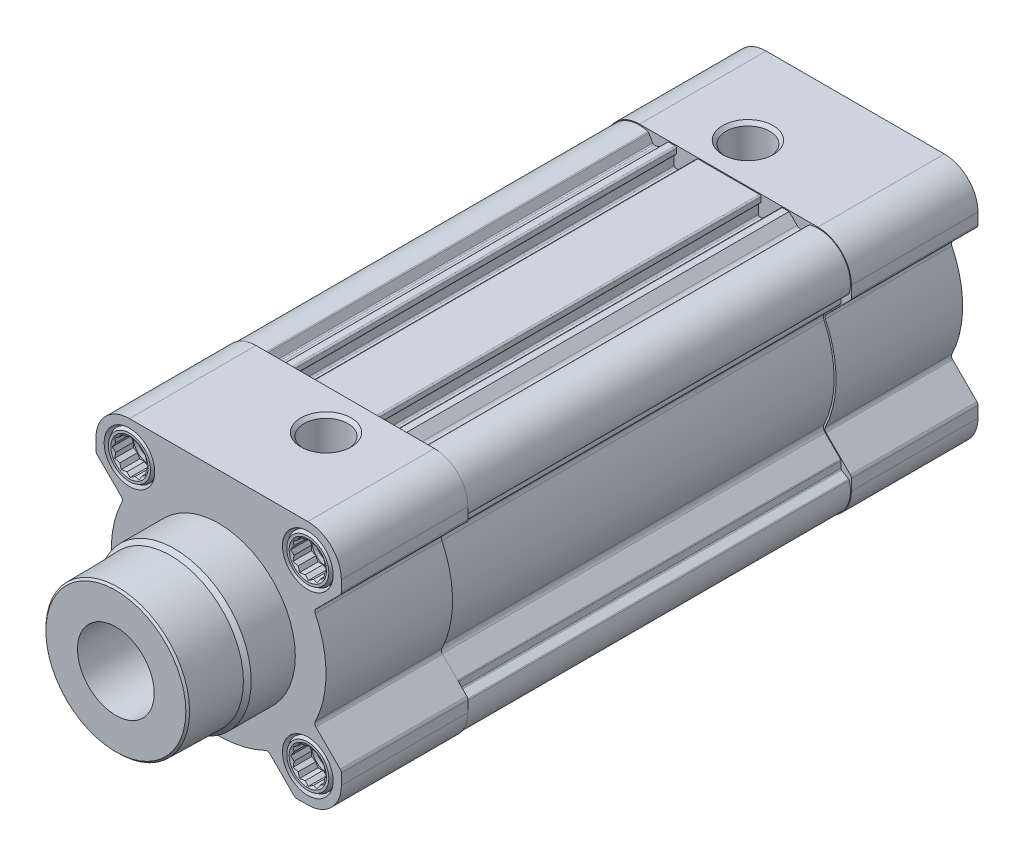
SolidWorks part; units mm, degrees
ref_plane "Front Plane" through (0, 0, 0) normal (0, 0, 1) x (1, 0, 0)
ref_plane "Top Plane" through (0, 0, 0) normal (0, 1, 0) x (1, 0, 0)
ref_plane "Right Plane" through (0, 0, 0) normal (1, 0, 0) x (0, 0, -1)
ref_plane "Plane1" through (0, 0, -33) normal (0, 0, 1) x (1, 0, 0)
sketch "Sketch1" plane through (0, 0, -33) normal (0, 0, 1) x (1, 0, 0)
  line L0 (-31.7071, 19.6863) -> (-25.385, 13.3642)
  line L1 (-25.385, -13.3642) -> (-31.7071, -19.6863)
  line L2 (-32, -20.3934) -> (-32, -23.25)
  line L3 (-23.25, -32) -> (-20.3934, -32)
  line L4 (-19.6863, -31.7071) -> (-13.3642, -25.385)
  line L5 (13.3642, -25.385) -> (19.6863, -31.7071)
  line L6 (20.3934, -32) -> (23.25, -32)
  line L7 (32, -23.25) -> (32, -20.3934)
  line L8 (31.7071, -19.6863) -> (25.385, -13.3642)
  line L9 (25.385, 13.3642) -> (31.7071, 19.6863)
  line L10 (32, 20.3934) -> (32, 23.25)
  line L11 (23.25, 32) -> (-23.25, 32)
  line L12 (-32, 23.25) -> (-32, 20.3934)
  arc A0 (-32, 20.3934) -> (-31.7071, 19.6863) centre (-31, 20.3934) ccw
  arc A1 (-25.385, 13.3642) -> (-25.1924, 12.2206) centre (-26.0921, 12.6571) cw
  arc A2 (-25.1924, 12.2206) -> (-25.1924, -12.2206) centre (0, 0) ccw
  arc A3 (-25.1924, -12.2206) -> (-25.385, -13.3642) centre (-26.0921, -12.6571) cw
  arc A4 (-31.7071, -19.6863) -> (-32, -20.3934) centre (-31, -20.3934) ccw
  arc A5 (-32, -23.25) -> (-23.25, -32) centre (-23.25, -23.25) ccw
  arc A6 (-20.3934, -32) -> (-19.6863, -31.7071) centre (-20.3934, -31) ccw
  arc A7 (-13.3642, -25.385) -> (-12.2206, -25.1924) centre (-12.6571, -26.0921) cw
  arc A8 (-12.2206, -25.1924) -> (12.2206, -25.1924) centre (0, 0) ccw
  arc A9 (12.2206, -25.1924) -> (13.3642, -25.385) centre (12.6571, -26.0921) cw
  arc A10 (19.6863, -31.7071) -> (20.3934, -32) centre (20.3934, -31) ccw
  arc A11 (23.25, -32) -> (32, -23.25) centre (23.25, -23.25) ccw
  arc A12 (32, -20.3934) -> (31.7071, -19.6863) centre (31, -20.3934) ccw
  arc A13 (25.385, -13.3642) -> (25.1924, -12.2206) centre (26.0921, -12.6571) cw
  arc A14 (25.1924, -12.2206) -> (25.1924, 12.2206) centre (0, 0) ccw
  arc A15 (25.1924, 12.2206) -> (25.385, 13.3642) centre (26.0921, 12.6571) cw
  arc A16 (31.7071, 19.6863) -> (32, 20.3934) centre (31, 20.3934) ccw
  arc A17 (32, 23.25) -> (23.25, 32) centre (23.25, 23.25) ccw
  arc A18 (-23.25, 32) -> (-32, 23.25) centre (-23.25, 23.25) ccw
extrude "Boss-Extrude1" add sketch "Sketch1" along normal blind 33
sketch "Sketch2" plane through (0, 0, -33) normal (0, 0, 1) x (1, 0, 0)
  line L0 (-31.75, 20.0827) -> (-25.2961, 13.6289)
  line L1 (-25.2961, -13.6289) -> (-31.75, -20.0827)
  line L2 (-31.75, -20.0827) -> (-31.75, -23.5)
  line L3 (-23.5, -31.75) -> (-20.0827, -31.75)
  line L4 (-20.0827, -31.75) -> (-13.6289, -25.2961)
  line L5 (13.6289, -25.2961) -> (20.0827, -31.75)
  line L6 (20.0827, -31.75) -> (23.5, -31.75)
  line L7 (31.75, -23.5) -> (31.75, -20.0827)
  line L8 (31.75, -20.0827) -> (25.2961, -13.6289)
  line L9 (25.2961, 13.6289) -> (31.75, 20.0827)
  line L10 (31.75, 20.0827) -> (31.75, 23.5)
  line L11 (23.5, 31.75) -> (-23.5, 31.75)
  line L12 (-31.75, 23.5) -> (-31.75, 20.0827)
  arc A0 (-25.2961, 13.6289) -> (-25.0028, 11.9226) centre (-26.3568, 12.5682) cw
  arc A1 (-25.0028, 11.9226) -> (-25.0028, -11.9226) centre (0, 0) ccw
  arc A2 (-25.0028, -11.9226) -> (-25.2961, -13.6289) centre (-26.3568, -12.5682) cw
  arc A3 (-31.75, -23.5) -> (-23.5, -31.75) centre (-23.5, -23.5) ccw
  arc A4 (-13.6289, -25.2961) -> (-11.9226, -25.0028) centre (-12.5682, -26.3568) cw
  arc A5 (-11.9226, -25.0028) -> (11.9226, -25.0028) centre (0, 0) ccw
  arc A6 (11.9226, -25.0028) -> (13.6289, -25.2961) centre (12.5682, -26.3568) cw
  arc A7 (23.5, -31.75) -> (31.75, -23.5) centre (23.5, -23.5) ccw
  arc A8 (25.2961, -13.6289) -> (25.0028, -11.9226) centre (26.3568, -12.5682) cw
  arc A9 (25.0028, -11.9226) -> (25.0028, 11.9226) centre (0, 0) ccw
  arc A10 (25.0028, 11.9226) -> (25.2961, 13.6289) centre (26.3568, 12.5682) cw
  arc A11 (31.75, 23.5) -> (23.5, 31.75) centre (23.5, 23.5) ccw
  arc A12 (-23.5, 31.75) -> (-31.75, 23.5) centre (-23.5, 23.5) ccw
extrude "Boss-Extrude2" add sketch "Sketch2" against normal blind 100
sketch "Sketch3" plane through (0, 0, -33) normal (0, 0, 1) x (1, 0, 0)
  line L0 (-38.4, -38.4) -> (38.4, -38.4)
  line L1 (38.4, -38.4) -> (38.4, 38.4)
  line L2 (38.4, 38.4) -> (-38.4, 38.4)
  line L3 (-38.4, 38.4) -> (-38.4, -38.4)
  line L4 (-20.8477, -31.2378) -> (-19.8155, -29.45)
  line L5 (-19.4691, -29.25) -> (-17.7484, -29.25)
  line L6 (-17.4656, -29.1328) -> (-13.4788, -25.146)
  line L7 (13.4788, -25.146) -> (17.4656, -29.1328)
  line L8 (17.7484, -29.25) -> (19.4691, -29.25)
  line L9 (19.8155, -29.45) -> (20.8477, -31.2378)
  line L10 (31.2378, -20.8477) -> (29.45, -19.8155)
  line L11 (29.25, -19.4691) -> (29.25, -17.7484)
  line L12 (29.1328, -17.4656) -> (25.146, -13.4788)
  line L13 (25.146, 13.4788) -> (29.1328, 17.4656)
  line L14 (29.25, 17.7484) -> (29.25, 19.4691)
  line L15 (29.45, 19.8155) -> (31.2378, 20.8477)
  line L16 (20.8477, 31.2378) -> (19.8155, 29.45)
  line L17 (19.4691, 29.25) -> (18.8713, 29.25)
  line L18 (17.8107, 29.6893) -> (15.75, 31.75)
  line L19 (15.75, 31.75) -> (14, 31.75)
  line L20 (13.6, 31.35) -> (13.6, 30.15)
  line L21 (13.8, 29.95) -> (14.05, 29.95)
  line L22 (14.25, 29.75) -> (14.25, 27.15)
  line L23 (13.85, 26.75) -> (8.15, 26.75)
  line L24 (7.75, 27.15) -> (7.75, 29.75)
  line L25 (7.95, 29.95) -> (8.2, 29.95)
  line L26 (8.4, 30.15) -> (8.4, 31.35)
  line L27 (8, 31.75) -> (-8, 31.75)
  line L28 (-8.4, 31.35) -> (-8.4, 30.15)
  line L29 (-8.2, 29.95) -> (-7.95, 29.95)
  line L30 (-7.75, 29.75) -> (-7.75, 27.15)
  line L31 (-8.15, 26.75) -> (-13.85, 26.75)
  line L32 (-14.25, 27.15) -> (-14.25, 29.75)
  line L33 (-14.05, 29.95) -> (-13.8, 29.95)
  line L34 (-13.6, 30.15) -> (-13.6, 31.35)
  line L35 (-14, 31.75) -> (-15.75, 31.75)
  line L36 (-15.75, 31.75) -> (-17.8107, 29.6893)
  line L37 (-18.8713, 29.25) -> (-19.4691, 29.25)
  line L38 (-19.8155, 29.45) -> (-20.8477, 31.2378)
  line L39 (-31.2378, 20.8477) -> (-29.45, 19.8155)
  line L40 (-29.25, 19.4691) -> (-29.25, 17.7484)
  line L41 (-29.1328, 17.4656) -> (-25.146, 13.4788)
  line L42 (-25.146, -13.4788) -> (-29.1328, -17.4656)
  line L43 (-29.25, -17.7484) -> (-29.25, -19.4691)
  line L44 (-29.45, -19.8155) -> (-31.2378, -20.8477)
  arc A0 (-31.4221, -21.0831) -> (-21.0831, -31.4221) centre (-23.4, -23.4) ccw
  arc A1 (-21.0831, -31.4221) -> (-20.8477, -31.2378) centre (-21.1941, -31.0378) ccw
  arc A2 (-19.8155, -29.45) -> (-19.4691, -29.25) centre (-19.4691, -29.65) cw
  arc A3 (-17.7484, -29.25) -> (-17.4656, -29.1328) centre (-17.7484, -28.85) ccw
  arc A4 (-13.4788, -25.146) -> (-11.7758, -24.8512) centre (-12.4181, -26.2067) cw
  arc A5 (-11.7758, -24.8512) -> (11.7758, -24.8512) centre (0, 0) ccw
  arc A6 (11.7758, -24.8512) -> (13.4788, -25.146) centre (12.4181, -26.2067) cw
  arc A7 (17.4656, -29.1328) -> (17.7484, -29.25) centre (17.7484, -28.85) ccw
  arc A8 (19.4691, -29.25) -> (19.8155, -29.45) centre (19.4691, -29.65) cw
  arc A9 (20.8477, -31.2378) -> (21.0831, -31.4221) centre (21.1941, -31.0378) ccw
  arc A10 (21.0831, -31.4221) -> (31.4221, -21.0831) centre (23.4, -23.4) ccw
  arc A11 (31.4221, -21.0831) -> (31.2378, -20.8477) centre (31.0378, -21.1941) ccw
  arc A12 (29.45, -19.8155) -> (29.25, -19.4691) centre (29.65, -19.4691) cw
  arc A13 (29.25, -17.7484) -> (29.1328, -17.4656) centre (28.85, -17.7484) ccw
  arc A14 (25.146, -13.4788) -> (24.8512, -11.7758) centre (26.2067, -12.4181) cw
  arc A15 (24.8512, -11.7758) -> (24.8512, 11.7758) centre (0, 0) ccw
  arc A16 (24.8512, 11.7758) -> (25.146, 13.4788) centre (26.2067, 12.4181) cw
  arc A17 (29.1328, 17.4656) -> (29.25, 17.7484) centre (28.85, 17.7484) ccw
  arc A18 (29.25, 19.4691) -> (29.45, 19.8155) centre (29.65, 19.4691) cw
  arc A19 (31.2378, 20.8477) -> (31.4221, 21.0831) centre (31.0378, 21.1941) ccw
  arc A20 (31.4221, 21.0831) -> (21.0831, 31.4221) centre (23.4, 23.4) ccw
  arc A21 (21.0831, 31.4221) -> (20.8477, 31.2378) centre (21.1941, 31.0378) ccw
  arc A22 (19.8155, 29.45) -> (19.4691, 29.25) centre (19.4691, 29.65) cw
  arc A23 (18.8713, 29.25) -> (17.8107, 29.6893) centre (18.8713, 30.75) cw
  arc A24 (14, 31.75) -> (13.6, 31.35) centre (14, 31.35) ccw
  arc A25 (13.6, 30.15) -> (13.8, 29.95) centre (13.8, 30.15) ccw
  arc A26 (14.05, 29.95) -> (14.25, 29.75) centre (14.05, 29.75) cw
  arc A27 (14.25, 27.15) -> (13.85, 26.75) centre (13.85, 27.15) cw
  arc A28 (8.15, 26.75) -> (7.75, 27.15) centre (8.15, 27.15) cw
  arc A29 (7.75, 29.75) -> (7.95, 29.95) centre (7.95, 29.75) cw
  arc A30 (8.2, 29.95) -> (8.4, 30.15) centre (8.2, 30.15) ccw
  arc A31 (8.4, 31.35) -> (8, 31.75) centre (8, 31.35) ccw
  arc A32 (-8, 31.75) -> (-8.4, 31.35) centre (-8, 31.35) ccw
  arc A33 (-8.4, 30.15) -> (-8.2, 29.95) centre (-8.2, 30.15) ccw
  arc A34 (-7.95, 29.95) -> (-7.75, 29.75) centre (-7.95, 29.75) cw
  arc A35 (-7.75, 27.15) -> (-8.15, 26.75) centre (-8.15, 27.15) cw
  arc A36 (-13.85, 26.75) -> (-14.25, 27.15) centre (-13.85, 27.15) cw
  arc A37 (-14.25, 29.75) -> (-14.05, 29.95) centre (-14.05, 29.75) cw
  arc A38 (-13.8, 29.95) -> (-13.6, 30.15) centre (-13.8, 30.15) ccw
  arc A39 (-13.6, 31.35) -> (-14, 31.75) centre (-14, 31.35) ccw
  arc A40 (-17.8107, 29.6893) -> (-18.8713, 29.25) centre (-18.8713, 30.75) cw
  arc A41 (-19.4691, 29.25) -> (-19.8155, 29.45) centre (-19.4691, 29.65) cw
  arc A42 (-20.8477, 31.2378) -> (-21.0831, 31.4221) centre (-21.1941, 31.0378) ccw
  arc A43 (-21.0831, 31.4221) -> (-31.4221, 21.0831) centre (-23.4, 23.4) ccw
  arc A44 (-31.4221, 21.0831) -> (-31.2378, 20.8477) centre (-31.0378, 21.1941) ccw
  arc A45 (-29.45, 19.8155) -> (-29.25, 19.4691) centre (-29.65, 19.4691) cw
  arc A46 (-29.25, 17.7484) -> (-29.1328, 17.4656) centre (-28.85, 17.7484) ccw
  arc A47 (-25.146, 13.4788) -> (-24.8512, 11.7758) centre (-26.2067, 12.4181) cw
  arc A48 (-24.8512, 11.7758) -> (-24.8512, -11.7758) centre (0, 0) ccw
  arc A49 (-24.8512, -11.7758) -> (-25.146, -13.4788) centre (-26.2067, -12.4181) cw
  arc A50 (-29.1328, -17.4656) -> (-29.25, -17.7484) centre (-28.85, -17.7484) ccw
  arc A51 (-29.25, -19.4691) -> (-29.45, -19.8155) centre (-29.65, -19.4691) cw
  arc A52 (-31.2378, -20.8477) -> (-31.4221, -21.0831) centre (-31.0378, -21.1941) ccw
extrude "Cut-Extrude1" cut sketch "Sketch3" against normal blind 100
ref_plane "Plane2" through (0, 0, -166) normal (0, 0, 1) x (1, 0, 0)
sketch "Sketch4" plane through (0, 0, -166) normal (0, 0, 1) x (1, 0, 0)
  line L0 (-31.7071, 19.6863) -> (-25.385, 13.3642)
  line L1 (-25.385, -13.3642) -> (-31.7071, -19.6863)
  line L2 (-32, -20.3934) -> (-32, -23.25)
  line L3 (-23.25, -32) -> (-20.3934, -32)
  line L4 (-19.6863, -31.7071) -> (-13.3642, -25.385)
  line L5 (13.3642, -25.385) -> (19.6863, -31.7071)
  line L6 (20.3934, -32) -> (23.25, -32)
  line L7 (32, -23.25) -> (32, -20.3934)
  line L8 (31.7071, -19.6863) -> (25.385, -13.3642)
  line L9 (25.385, 13.3642) -> (31.7071, 19.6863)
  line L10 (32, 20.3934) -> (32, 23.25)
  line L11 (23.25, 32) -> (-23.25, 32)
  line L12 (-32, 23.25) -> (-32, 20.3934)
  arc A0 (-32, 20.3934) -> (-31.7071, 19.6863) centre (-31, 20.3934) ccw
  arc A1 (-25.385, 13.3642) -> (-25.1924, 12.2206) centre (-26.0921, 12.6571) cw
  arc A2 (-25.1924, 12.2206) -> (-25.1924, -12.2206) centre (0, 0) ccw
  arc A3 (-25.1924, -12.2206) -> (-25.385, -13.3642) centre (-26.0921, -12.6571) cw
  arc A4 (-31.7071, -19.6863) -> (-32, -20.3934) centre (-31, -20.3934) ccw
  arc A5 (-32, -23.25) -> (-23.25, -32) centre (-23.25, -23.25) ccw
  arc A6 (-20.3934, -32) -> (-19.6863, -31.7071) centre (-20.3934, -31) ccw
  arc A7 (-13.3642, -25.385) -> (-12.2206, -25.1924) centre (-12.6571, -26.0921) cw
  arc A8 (-12.2206, -25.1924) -> (12.2206, -25.1924) centre (0, 0) ccw
  arc A9 (12.2206, -25.1924) -> (13.3642, -25.385) centre (12.6571, -26.0921) cw
  arc A10 (19.6863, -31.7071) -> (20.3934, -32) centre (20.3934, -31) ccw
  arc A11 (23.25, -32) -> (32, -23.25) centre (23.25, -23.25) ccw
  arc A12 (32, -20.3934) -> (31.7071, -19.6863) centre (31, -20.3934) ccw
  arc A13 (25.385, -13.3642) -> (25.1924, -12.2206) centre (26.0921, -12.6571) cw
  arc A14 (25.1924, -12.2206) -> (25.1924, 12.2206) centre (0, 0) ccw
  arc A15 (25.1924, 12.2206) -> (25.385, 13.3642) centre (26.0921, 12.6571) cw
  arc A16 (31.7071, 19.6863) -> (32, 20.3934) centre (31, 20.3934) ccw
  arc A17 (32, 23.25) -> (23.25, 32) centre (23.25, 23.25) ccw
  arc A18 (-23.25, 32) -> (-32, 23.25) centre (-23.25, 23.25) ccw
extrude "Boss-Extrude3" add sketch "Sketch4" along normal blind 33
ref_plane "Plane3" through (0, 0, 0) normal (0.7071, 0.7071, 0) x (0.7071, -0.7071, 0)
ref_plane "Plane4" through (0, 0, 0) normal (-0.7071, 0.7071, 0) x (0.7071, 0.7071, 0)
sketch "Sketch5" plane through (0, 0, 0) normal (1, 0, 0) x (0, 0, -1)
  line L0 (-26.8, 0) -> (-26.8, 18.2417)
  line L1 (-26.8, 18.2417) -> (-26.3, 18.7417)
  line L2 (-26.3, 18.7417) -> (-12.5178, 18.9822)
  line L3 (-12.5178, 18.9822) -> (-11.5, 20)
  line L4 (-11.5, 20) -> (0, 20)
  line L5 (0, 20) -> (0, 0)
  line L6 (0, 0) -> (-26.8, 0)
  line L7 (0, 0) -> (-26.8, 0) construction
revolve "Revolve1" add sketch "Sketch5" angle 360 about L7 reverse direction yes
ref_plane "Plane5" through (5.5, 0, 0) normal (1, 0, 0) x (0, 0, -1)
hole_wizard "Hole1" positions "Sketch7" profile "Sketch6" legacy
sketch "Sketch7" plane through (0, 32, 0) normal (0, 1, 0) x (1, 0, 0)
  point P0 (5.5, 22.5)
sketch "Sketch6" plane through (5.5, 32, -22.5) normal (1, 0, 0) x (0, 0, 1)
  line L0 (0, 0) -> (0, 32)
  line L1 (0, 32) -> (5.7225, 32)
  line L2 (5.7225, 32) -> (5.7225, 0.856)
  line L3 (5.7225, 0.856) -> (6.5785, 0)
  line L4 (6.5785, 0) -> (0, 0)
  line L5 (0, -6.4453) -> (0, 115.525) construction
  line L6 (-5.7225, 0.856) -> (-6.5785, 0) construction
  dimension "Diameter" = 11.445
  dimension "Depth" = 32
  dimension "C-Sink Angle" = 90
  dimension "C-Sink Diameter" = 13.157
cosmetic thread "Cosmetic Thread1" parameters "D1"=12, "D2"=13.157
ref_plane "Plane6" through (-10.4, 0, 0) normal (1, 0, 0) x (0, 0, -1)
ref_plane "Plane7" through (23.25, 0, 0) normal (1, 0, 0) x (0, 0, -1)
sketch "Sketch8" plane through (23.25, 0, 0) normal (1, 0, 0) x (0, 0, -1)
  line L0 (0, 23.25) -> (0, 29.85)
  line L1 (0, 29.85) -> (24.5, 29.85)
  line L2 (24.5, 29.85) -> (24.5, 23.25)
  line L3 (24.5, 23.25) -> (0, 23.25)
  line L4 (24.5, 23.25) -> (0, 23.25) construction
revolve "Cut-Revolve1" cut sketch "Sketch8" angle 360 about L4 reverse direction yes
sketch "Sketch9" plane through (0, 0, 0) normal (0, 0, 1) x (1, 0, 0)
  line L0 (23.25, 23.25) -> (-23.25, 23.25)
  line L1 (23.25, 23.25) -> (23.25, -23.25)
pattern_linear "LPattern1" count 2 spacing 46.5 along (-1, 0, 0) count 2 spacing 46.5 along (0, -1, 0) of "Cut-Revolve1"
sketch "Sketch10" plane through (23.25, 0, 0) normal (1, 0, 0) x (0, 0, -1)
  line L0 (0, 23.25) -> (0, 28.7304)
  line L1 (0, 28.7304) -> (0.9, 29.25)
  line L2 (0.9, 29.25) -> (24.5, 29.25)
  line L3 (24.5, 29.25) -> (24.5, 23.25)
  line L4 (24.5, 23.25) -> (0, 23.25)
  line L5 (24.5, 23.25) -> (0, 23.25) construction
revolve "Revolve2" add sketch "Sketch10" angle 360 about L5 reverse direction yes
sketch "Sketch11" plane through (0, 0, 0) normal (0, 0, 1) x (1, 0, 0)
  line L0 (23.25, 23.25) -> (-23.25, 23.25)
  line L1 (23.25, 23.25) -> (23.25, -23.25)
pattern_linear "LPattern2" count 2 spacing 46.5 along (-1, 0, 0) count 2 spacing 46.5 along (0, -1, 0) of "Revolve2"
sketch "Sketch12" plane through (23.25, 0, 0) normal (1, 0, 0) x (0, 0, -1)
  line L0 (0, 23.25) -> (0, 28.1)
  line L1 (0, 28.1) -> (0.4907, 27.25)
  line L2 (0.4907, 27.25) -> (6, 27.25)
  line L3 (6, 27.25) -> (6.6765, 26.5735)
  line L4 (6.6765, 26.5735) -> (20.2, 26.5735)
  line L5 (20.2, 26.5735) -> (22.1188, 23.25)
  line L6 (22.1188, 23.25) -> (0, 23.25)
  line L7 (22.1188, 23.25) -> (0, 23.25) construction
revolve "Cut-Revolve2" cut sketch "Sketch12" angle 360 about L7 reverse direction yes
cosmetic thread "Cosmetic Thread2" parameters "D1"=11, "D2"=8
sketch "Sketch13" plane through (0, 0, 0) normal (0, 0, 1) x (1, 0, 0)
  line L0 (18.6312, 23.25) -> (19.25, 22.1782)
  line L1 (19.25, 22.1782) -> (19.25, 20.9406)
  line L2 (19.25, 20.9406) -> (20.3218, 20.3218)
  line L3 (20.3218, 20.3218) -> (20.9406, 19.25)
  line L4 (20.9406, 19.25) -> (22.1782, 19.25)
  line L5 (22.1782, 19.25) -> (23.25, 18.6312)
  line L6 (23.25, 18.6312) -> (24.3218, 19.25)
  line L7 (24.3218, 19.25) -> (25.5594, 19.25)
  line L8 (25.5594, 19.25) -> (26.1782, 20.3218)
  line L9 (26.1782, 20.3218) -> (27.25, 20.9406)
  line L10 (27.25, 20.9406) -> (27.25, 22.1782)
  line L11 (27.25, 22.1782) -> (27.8688, 23.25)
  line L12 (27.8688, 23.25) -> (27.25, 24.3218)
  line L13 (27.25, 24.3218) -> (27.25, 25.5594)
  line L14 (27.25, 25.5594) -> (26.1782, 26.1782)
  line L15 (26.1782, 26.1782) -> (25.5594, 27.25)
  line L16 (25.5594, 27.25) -> (24.3218, 27.25)
  line L17 (24.3218, 27.25) -> (23.25, 27.8688)
  line L18 (23.25, 27.8688) -> (22.1782, 27.25)
  line L19 (22.1782, 27.25) -> (20.9406, 27.25)
  line L20 (20.9406, 27.25) -> (20.3218, 26.1782)
  line L21 (20.3218, 26.1782) -> (19.25, 25.5594)
  line L22 (19.25, 25.5594) -> (19.25, 24.3218)
  line L23 (19.25, 24.3218) -> (18.6312, 23.25)
extrude "Cut-Extrude2" cut sketch "Sketch13" along normal blind 5 and the other way blind 5
sketch "Sketch14" plane through (0, 0, 0) normal (0, 0, 1) x (1, 0, 0)
  line L0 (23.25, 23.25) -> (-23.25, 23.25)
  line L1 (23.25, 23.25) -> (23.25, -23.25)
pattern_linear "LPattern3" count 2 spacing 46.5 along (-1, 0, 0) count 2 spacing 46.5 along (0, -1, 0) of "Cut-Revolve2"
sketch "Sketch15" plane through (0, 0, 0) normal (0, 0, 1) x (1, 0, 0)
  line L0 (23.25, 23.25) -> (-23.25, 23.25)
  line L1 (23.25, 23.25) -> (23.25, -23.25)
pattern_linear "LPattern4" count 2 spacing 46.5 along (-1, 0, 0) count 2 spacing 46.5 along (0, -1, 0) of "Cut-Extrude2"
ref_plane "Plane8" through (0, 0, -166) normal (0, 0, 1) x (1, 0, 0)
sketch "Sketch16" plane through (0, 0, 0) normal (1, 0, 0) x (0, 0, -1)
  line L0 (166, 0) -> (166, 20)
  line L1 (166, 20) -> (169.5, 20)
  line L2 (169.5, 20) -> (170, 19.5)
  line L3 (170, 19.5) -> (170, 0)
  line L4 (170, 0) -> (166, 0)
  line L5 (170, 0) -> (166, 0) construction
revolve "Revolve3" add sketch "Sketch16" angle 360 about L5 reverse direction yes
ref_plane "Plane9" through (-5.5, 0, 0) normal (1, 0, 0) x (0, 0, -1)
hole_wizard "Hole2" positions "Sketch18" profile "Sketch17" legacy
sketch "Sketch18" plane through (0, 32, 0) normal (0, 1, 0) x (1, 0, 0)
  point P0 (-5.5, 143.5)
sketch "Sketch17" plane through (-5.5, 32, -143.5) normal (1, 0, 0) x (0, 0, 1)
  line L0 (0, 0) -> (0, 32)
  line L1 (0, 32) -> (5.7225, 32)
  line L2 (5.7225, 32) -> (5.7225, 0.856)
  line L3 (5.7225, 0.856) -> (6.5785, 0)
  line L4 (6.5785, 0) -> (0, 0)
  line L5 (0, -6.4453) -> (0, 115.525) construction
  line L6 (-5.7225, 0.856) -> (-6.5785, 0) construction
  dimension "Diameter" = 11.445
  dimension "Depth" = 32
  dimension "C-Sink Angle" = 90
  dimension "C-Sink Diameter" = 13.157
cosmetic thread "Cosmetic Thread3" parameters "D1"=12, "D2"=13.157
ref_plane "Plane10" through (10.4, 0, 0) normal (1, 0, 0) x (0, 0, -1)
hole_wizard "Hole3" positions "Sketch20" profile "Sketch19" legacy
sketch "Sketch20" plane through (0, 0, -166) normal (0, 0, -1) x (-1, 0, 0)
  point P0 (-23.25, 23.25)
sketch "Sketch19" plane through (23.25, 23.25, -166) normal (1, 0, 0) x (0, 1, 0)
  line L0 (0, 0) -> (0, 24.5)
  line L1 (0, 24.5) -> (6.6, 24.5)
  line L2 (6.6, 24.5) -> (6.6, 0)
  line L3 (6.6, 0) -> (0, 0)
  line L4 (0, 110) -> (0, -10) construction
  dimension "Diameter" = 13.2
  dimension "Depth" = 24.5
sketch "Sketch21" plane through (0, 0, -166) normal (0, 0, 1) x (1, 0, 0)
  line L0 (23.25, 23.25) -> (-23.25, 23.25)
  line L1 (23.25, 23.25) -> (23.25, -23.25)
pattern_linear "LPattern5" count 2 spacing 46.5 along (-1, 0, 0) count 2 spacing 46.5 along (0, -1, 0) of "Hole3"
sketch "Sketch22" plane through (23.25, 0, 0) normal (1, 0, 0) x (0, 0, -1)
  line L0 (141.5, 23.25) -> (141.5, 29.25)
  line L1 (141.5, 29.25) -> (165.1, 29.25)
  line L2 (165.1, 29.25) -> (166, 28.7304)
  line L3 (166, 28.7304) -> (166, 23.25)
  line L4 (166, 23.25) -> (141.5, 23.25)
  line L5 (166, 23.25) -> (141.5, 23.25) construction
revolve "Revolve4" add sketch "Sketch22" angle 360 about L5 reverse direction yes
sketch "Sketch23" plane through (0, 0, -166) normal (0, 0, 1) x (1, 0, 0)
  line L0 (23.25, 23.25) -> (-23.25, 23.25)
  line L1 (23.25, 23.25) -> (23.25, -23.25)
pattern_linear "LPattern6" count 2 spacing 46.5 along (-1, 0, 0) count 2 spacing 46.5 along (0, -1, 0) of "Revolve4"
sketch "Sketch24" plane through (23.25, 0, 0) normal (1, 0, 0) x (0, 0, -1)
  line L0 (143.8812, 23.25) -> (145.8, 26.5735)
  line L1 (145.8, 26.5735) -> (159.3235, 26.5735)
  line L2 (159.3235, 26.5735) -> (160, 27.25)
  line L3 (160, 27.25) -> (165.5093, 27.25)
  line L4 (165.5093, 27.25) -> (166, 28.1)
  line L5 (166, 28.1) -> (166, 23.25)
  line L6 (166, 23.25) -> (143.8812, 23.25)
  line L7 (166, 23.25) -> (143.8812, 23.25) construction
revolve "Cut-Revolve3" cut sketch "Sketch24" angle 360 about L7 reverse direction yes
cosmetic thread "Cosmetic Thread4" parameters "D1"=11, "D2"=8
sketch "Sketch25" plane through (0, 0, -166) normal (0, 0, 1) x (1, 0, 0)
  line L0 (23.25, 23.25) -> (-23.25, 23.25)
  line L1 (23.25, 23.25) -> (23.25, -23.25)
pattern_linear "LPattern7" count 2 spacing 46.5 along (-1, 0, 0) count 2 spacing 46.5 along (0, -1, 0) of "Cut-Revolve3"
sketch "Sketch26" plane through (0, 0, -166) normal (0, 0, 1) x (1, 0, 0)
  line L0 (18.6312, 23.25) -> (19.25, 22.1782)
  line L1 (19.25, 22.1782) -> (19.25, 20.9406)
  line L2 (19.25, 20.9406) -> (20.3218, 20.3218)
  line L3 (20.3218, 20.3218) -> (20.9406, 19.25)
  line L4 (20.9406, 19.25) -> (22.1782, 19.25)
  line L5 (22.1782, 19.25) -> (23.25, 18.6312)
  line L6 (23.25, 18.6312) -> (24.3218, 19.25)
  line L7 (24.3218, 19.25) -> (25.5594, 19.25)
  line L8 (25.5594, 19.25) -> (26.1782, 20.3218)
  line L9 (26.1782, 20.3218) -> (27.25, 20.9406)
  line L10 (27.25, 20.9406) -> (27.25, 22.1782)
  line L11 (27.25, 22.1782) -> (27.8688, 23.25)
  line L12 (27.8688, 23.25) -> (27.25, 24.3218)
  line L13 (27.25, 24.3218) -> (27.25, 25.5594)
  line L14 (27.25, 25.5594) -> (26.1782, 26.1782)
  line L15 (26.1782, 26.1782) -> (25.5594, 27.25)
  line L16 (25.5594, 27.25) -> (24.3218, 27.25)
  line L17 (24.3218, 27.25) -> (23.25, 27.8688)
  line L18 (23.25, 27.8688) -> (22.1782, 27.25)
  line L19 (22.1782, 27.25) -> (20.9406, 27.25)
  line L20 (20.9406, 27.25) -> (20.3218, 26.1782)
  line L21 (20.3218, 26.1782) -> (19.25, 25.5594)
  line L22 (19.25, 25.5594) -> (19.25, 24.3218)
  line L23 (19.25, 24.3218) -> (18.6312, 23.25)
extrude "Cut-Extrude3" cut sketch "Sketch26" along normal blind 5 and the other way blind 5
sketch "Sketch27" plane through (0, 0, -166) normal (0, 0, 1) x (1, 0, 0)
  line L0 (23.25, 23.25) -> (-23.25, 23.25)
  line L1 (23.25, 23.25) -> (23.25, -23.25)
pattern_linear "LPattern8" count 2 spacing 46.5 along (-1, 0, 0) count 2 spacing 46.5 along (0, -1, 0) of "Cut-Extrude3"
ref_plane "Plane11" through (0, 0, 0) normal (0.7071, 0.7071, 0) x (0.7071, -0.7071, 0)
ref_plane "Plane12" through (0, 0, -152) normal (0, 0, 1) x (1, 0, 0)
ref_plane "Plane13" through (0, 0, -133) normal (0, 0, 1) x (1, 0, 0)
sketch "Sketch28" plane through (0, 0, 0) normal (1, 0, 0) x (0, 0, -1)
  line L0 (-26.8, 0) -> (-26.8, 10)
  line L1 (-26.8, 10) -> (56.3333, 10)
  line L2 (56.3333, 10) -> (56.3333, 25)
  line L3 (56.3333, 25) -> (133, 25)
  line L4 (133, 25) -> (133, 0)
  line L5 (133, 0) -> (-26.8, 0)
  line L6 (133, 0) -> (-26.8, 0) construction
revolve "Cut-Revolve4" cut sketch "Sketch28" angle 360 about L6 reverse direction yes
ref_plane "Plane14" through (0, 0, 26.8) normal (0, 0, 1) x (1, 0, 0)
ref_plane "Plane15" through (0, 0, 0) normal (0, 0, 1) x (1, 0, 0)
ref_plane "Plane16" through (0, 0, -166) normal (0, 0, 1) x (1, 0, 0)
ref_plane "Plane17" through (0, 0, -50) normal (0, 0, 1) x (1, 0, 0)
ref_plane "Plane18" through (0, 32, 0) normal (0, 1, 0) x (1, 0, 0)
ref_plane "Plane19" through (0, 0, -33) normal (0, 0, 1) x (1, 0, 0)
ref_plane "Plane20" through (0, 0, 0) normal (1, 0, 0) x (0, 0, -1)
ref_plane "Plane21" through (0, 32, 0) normal (0, 1, 0) x (1, 0, 0)
ref_plane "Plane22" through (0, 0, 0) normal (0, 0, 1) x (1, 0, 0)
ref_plane "Plane23" through (0, 0, -166) normal (0, 0, 1) x (1, 0, 0)
ref_plane "2DUMMY XY" through (0, 0, 0) normal (0, 0, -1) x (-1, 0, 0)
ref_plane "2DUMMY XZ" through (0, 0, 0) normal (0, 1, 0) x (1, 0, 0)
ref_plane "2DUMMY YZ" through (0, 0, 0) normal (1, 0, 0) x (0, 0, -1)
ref_axis "2DUMMY X" through (-80.9, 0, 0) along (1, 0, 0)
ref_axis "2DUMMY Y" through (0, 50, 0) along (0, -1, 0)
ref_axis "2DUMMY Z" through (0, 0, -80.9) along (0, 0, 1)
sketch3d "2DUMMY"
  point P0 (0, 0, 0)
ref_plane "2P XY" through (0, 0, -133) normal (0, 0, 1) x (1, 0, 0)
ref_plane "2P XZ" through (0, 0, 0) normal (0, -1, 0) x (-1, 0, 0)
ref_plane "2P YZ" through (0, 0, 0) normal (1, 0, 0) x (0, 0, -1)
ref_axis "2P X" through (-80.9, 0, -133) along (1, 0, 0)
ref_axis "2P Y" through (0, -50, -133) along (0, 1, 0)
ref_axis "2P Z" through (0, 0, 80.9) along (0, 0, -1)
sketch3d "2P"
  point P0 (0, 0, -133)
ref_plane "FDT_FRONT XY" through (0, 0, 0) normal (0, 0, 1) x (1, 0, 0)
ref_plane "FDT_FRONT XZ" through (0, 0, 0) normal (0, -1, 0) x (-1, 0, 0)
ref_plane "FDT_FRONT YZ" through (0, 0, 0) normal (1, 0, 0) x (0, 0, -1)
ref_axis "FDT_FRONT X" through (-80.9, 0, 0) along (1, 0, 0)
ref_axis "FDT_FRONT Y" through (0, -50, 0) along (0, 1, 0)
ref_axis "FDT_FRONT Z" through (0, 0, 80.9) along (0, 0, -1)
sketch3d "FDT_FRONT"
  point P0 (0, 0, 0)
ref_plane "FDT_QSFRONT XY" through (0, 32, 0) normal (0, 1, 0) x (1, 0, 0)
ref_plane "FDT_QSFRONT XZ" through (0, 0, -22.5) normal (0, 0, 1) x (1, 0, 0)
ref_plane "FDT_QSFRONT YZ" through (5.5, 0, 0) normal (1, 0, 0) x (0, 0, -1)
ref_axis "FDT_QSFRONT X" through (-80.9, 32, -22.5) along (1, 0, 0)
ref_axis "FDT_QSFRONT Y" through (5.5, 32, 50) along (0, 0, -1)
ref_axis "FDT_QSFRONT Z" through (5.5, 50, -22.5) along (0, -1, 0)
sketch3d "FDT_QSFRONT"
  point P0 (5.5, 32, -22.5)
ref_plane "FDT_QSREAR XY" through (0, 32, 0) normal (0, 1, 0) x (1, 0, 0)
ref_plane "FDT_QSREAR XZ" through (0, 0, -143.5) normal (0, 0, 1) x (1, 0, 0)
ref_plane "FDT_QSREAR YZ" through (-5.5, 0, 0) normal (1, 0, 0) x (0, 0, -1)
ref_axis "FDT_QSREAR X" through (-80.9, 32, -143.5) along (1, 0, 0)
ref_axis "FDT_QSREAR Y" through (-5.5, 32, 50) along (0, 0, -1)
ref_axis "FDT_QSREAR Z" through (-5.5, 50, -143.5) along (0, -1, 0)
sketch3d "FDT_QSREAR"
  point P0 (-5.5, 32, -143.5)
ref_plane "FDT_REAR XY" through (0, 0, -166) normal (0, 0, 1) x (1, 0, 0)
ref_plane "FDT_REAR XZ" through (0, 0, 0) normal (0, -1, 0) x (-1, 0, 0)
ref_plane "FDT_REAR YZ" through (0, 0, 0) normal (1, 0, 0) x (0, 0, -1)
ref_axis "FDT_REAR X" through (-80.9, 0, -166) along (1, 0, 0)
ref_axis "FDT_REAR Y" through (0, -50, -166) along (0, 1, 0)
ref_axis "FDT_REAR Z" through (0, 0, 80.9) along (0, 0, -1)
sketch3d "FDT_REAR"
  point P0 (0, 0, -166)
ref_plane "FDT_SLOT1 XY" through (0, 26.75, 0) normal (0, 1, 0) x (1, 0, 0)
ref_plane "FDT_SLOT1 XZ" through (0, 0, -83) normal (0, 0, 1) x (1, 0, 0)
ref_plane "FDT_SLOT1 YZ" through (11, 0, 0) normal (1, 0, 0) x (0, 0, -1)
ref_axis "FDT_SLOT1 X" through (-80.9, 26.75, -83) along (1, 0, 0)
ref_axis "FDT_SLOT1 Y" through (11, 26.75, 50) along (0, 0, -1)
ref_axis "FDT_SLOT1 Z" through (11, 50, -83) along (0, -1, 0)
sketch3d "FDT_SLOT1"
  point P0 (11, 26.75, -83)
ref_plane "FDT_SLOT2 XY" through (0, 26.75, 0) normal (0, 1, 0) x (1, 0, 0)
ref_plane "FDT_SLOT2 XZ" through (0, 0, -83) normal (0, 0, 1) x (1, 0, 0)
ref_plane "FDT_SLOT2 YZ" through (-11, 0, 0) normal (1, 0, 0) x (0, 0, -1)
ref_axis "FDT_SLOT2 X" through (-80.9, 26.75, -83) along (1, 0, 0)
ref_axis "FDT_SLOT2 Y" through (-11, 26.75, 50) along (0, 0, -1)
ref_axis "FDT_SLOT2 Z" through (-11, 50, -83) along (0, -1, 0)
sketch3d "FDT_SLOT2"
  point P0 (-11, 26.75, -83)
ref_plane "FDT_TRUNNMOUNT XY" through (0, 0, -50) normal (0, 0, 1) x (1, 0, 0)
ref_plane "FDT_TRUNNMOUNT XZ" through (0, 0, 0) normal (0, -1, 0) x (-1, 0, 0)
ref_plane "FDT_TRUNNMOUNT YZ" through (0, 0, 0) normal (1, 0, 0) x (0, 0, -1)
ref_axis "FDT_TRUNNMOUNT X" through (-80.9, 0, -50) along (1, 0, 0)
ref_axis "FDT_TRUNNMOUNT Y" through (0, -50, -50) along (0, 1, 0)
ref_axis "FDT_TRUNNMOUNT Z" through (0, 0, 80.9) along (0, 0, -1)
sketch3d "FDT_TRUNNMOUNT"
  point P0 (0, 0, -50)
ref_plane "TO_C XY" through (0, 0, -166) normal (0, 0, 1) x (1, 0, 0)
ref_plane "TO_C XZ" through (0, 0, 0) normal (0, -1, 0) x (-1, 0, 0)
ref_plane "TO_C YZ" through (0, 0, 0) normal (1, 0, 0) x (0, 0, -1)
ref_axis "TO_C X" through (-80.9, 0, -166) along (1, 0, 0)
ref_axis "TO_C Y" through (0, -50, -166) along (0, 1, 0)
ref_axis "TO_C Z" through (0, 0, 80.9) along (0, 0, -1)
sketch3d "TO_C"
  point P0 (0, 0, -166)
ref_plane "TO_P2 XY" through (0, 0, 26.8) normal (0, 0, 1) x (1, 0, 0)
ref_plane "TO_P2 XZ" through (0, 0, 0) normal (0, -1, 0) x (-1, 0, 0)
ref_plane "TO_P2 YZ" through (0, 0, 0) normal (1, 0, 0) x (0, 0, -1)
ref_axis "TO_P2 X" through (-80.9, 0, 26.8) along (1, 0, 0)
ref_axis "TO_P2 Y" through (0, -50, 26.8) along (0, 1, 0)
ref_axis "TO_P2 Z" through (0, 0, 80.9) along (0, 0, -1)
sketch3d "TO_P2"
  point P0 (0, 0, 26.8)
